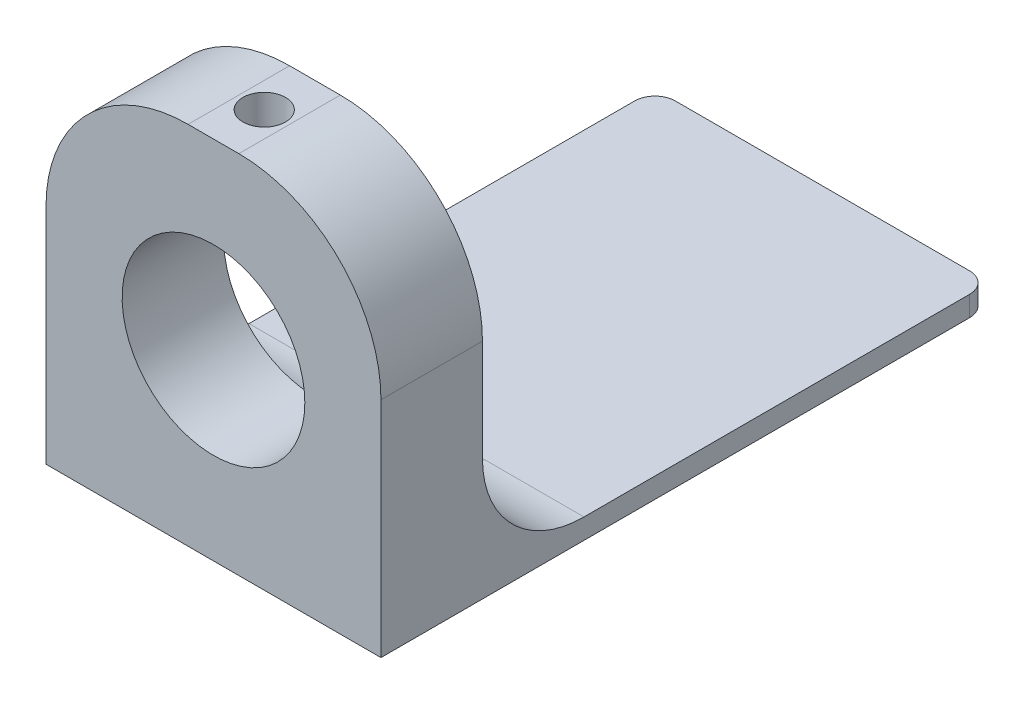
SolidWorks part; units mm, degrees
ref_plane "Front Plane" through (0, 0, 0) normal (0, 0, 1) x (1, 0, 0)
ref_plane "Top Plane" through (0, 0, 0) normal (0, 1, 0) x (1, 0, 0)
ref_plane "Right Plane" through (0, 0, 0) normal (1, 0, 0) x (0, 0, -1)
sketch "Sketch1" plane through (0, 0, 0) normal (0, 0, 1) x (1, 0, 0)
  line L4 (-16.5, -18) -> (16.5, -18)
  line L5 (-16.5, -18) -> (-16.5, 18)
  line L6 (-16.5, 18) -> (16.5, 18)
  line L7 (16.5, -18) -> (16.5, 18)
  circle A0 centre (0, 0) radius 9
  point P10 (0, -18)
  dimension "D1" = 18
  dimension "D2" = 33
  dimension "D3" = 18
  dimension "D4" = 18
extrude "Boss-Extrude2" add sketch "Sketch1" along normal blind 10
sketch "Sketch2" plane through (0, 18, 0) normal (0, 1, 0) x (1, 0, 0)
  line L0 (16.5, 0) -> (-16.5, 0) construction
  circle A0 centre (0, -5) radius 2.1
  dimension "D1" = 4.2
  dimension "D2" = 5
extrude "Cut-Extrude1" cut sketch "Sketch2" against normal up to next
sketch "Sketch3" plane through (0, -18, 0) normal (0, -1, 0) x (-1, 0, 0)
  line L0 (-16.5, -10) -> (-16.5, 0) construction
  line L1 (16.5, 0) -> (-16.5, 0)
  line L2 (16.5, 0) -> (16.5, 50)
  line L3 (16.5, 50) -> (-16.5, 50)
  line L4 (-16.5, 0) -> (-16.5, 50)
  dimension "D1" = 60
extrude "Boss-Extrude3" add sketch "Sketch3" against normal blind 2
fillet "Fillet1" radius 10 1 edges at (0, -16, 0)
fillet "Fillet2" radius 14 2 edges at (16.5, 18, 5) (-16.5, 18, 5)
fillet "Fillet3" radius 2 2 edges at (16.5, -17, -50) (-16.5, -17, -50)
equation "\"D4@Sketch1\"=\"D1@Sketch1\""
equation "\"D3@Sketch1\"=\"D1@Sketch1\""
